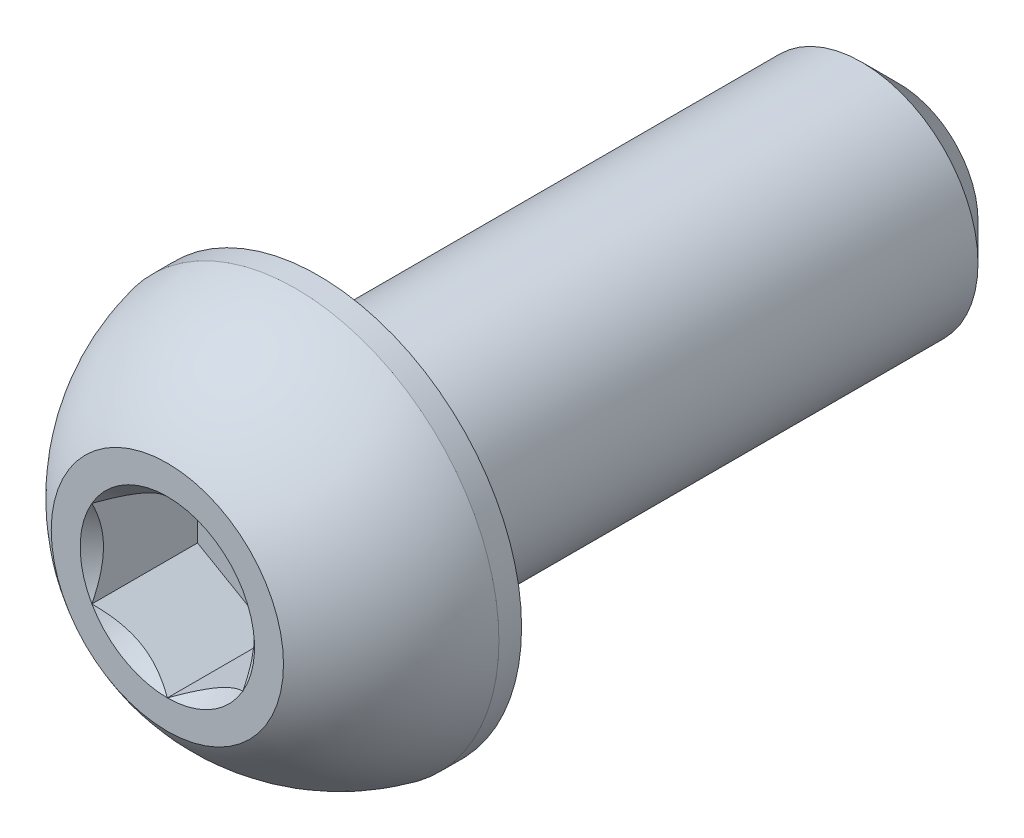
SolidWorks part; units mm, degrees
material "Alloy Steel"
ref_plane "Front Plane" through (0, 0, 0) normal (0, 0, 1) x (1, 0, 0)
ref_plane "Top Plane" through (0, 0, 0) normal (0, 1, 0) x (1, 0, 0)
ref_plane "Right Plane" through (0, 0, 0) normal (1, 0, 0) x (0, 0, -1)
sketch "Sketch1" plane through (0, 0, 0) normal (1, 0, 0) x (0, 0, -1)
  line L0 (-3.15, 0) -> (3.15, 0) construction
  line L1 (-1.85, 1.75) -> (-1.85, -1.75) construction
  line L2 (3.15, 1) -> (3.15, -1) construction
  line L3 (3.125, 1.0433) -> (3.325, 0.6969) construction
  line L4 (3.325, 0.6969) -> (3.525, 1.0433) construction
  line L5 (3.525, 1.0433) -> (3.125, 1.0433) construction
  line L6 (3.15, 1) -> (3.5, 1) construction
  line L7 (3.325, 1.0433) -> (3.325, 1) construction
  line L8 (3.325, 1) -> (3.325, 0.7402) construction
  line L9 (3.325, 0.7402) -> (3.325, 0.6969) construction
  line L10 (3.3, 0.7402) -> (3.35, 0.7402)
  line L11 (3.1375, 1.0217) -> (3.5125, 1.0217)
  line L12 (3.35, 0.7402) -> (3.5125, 1.0217)
  line L13 (3.3, 0.7402) -> (3.1375, 1.0217)
  line L14 (-3.15, 0.65) -> (-3.15, -0.65) construction
  line L15 (3.15, 1) -> (-1.85, 1) construction
  point P3 (-1.85, 0)
  point P6 (-2.24, 0)
  point P21 (3.325, 1.0217)
  point P24 (-2.045, 1.75)
  point P25 (2.15, -1)
  point P26 (-3.15, 1)
  dimension "Head Height" = 1.3
  dimension "Length" = 5
  dimension "Head Dia" = 3.5
  dimension "Thread Dia" = 2
  dimension "Pitch" = 0.4
  dimension "D2" = 0.05
  dimension "Drive Size" = 1.3
  dimension "D1" = 0.91
  dimension "D3" = 0.195
  dimension "D4" = 1
sketch "Sketch2" plane through (0, 0, 0) normal (1, 0, 0) x (0, 0, -1)
  line L0 (-3.15, 0) -> (3.15, 0)
  line L1 (3.15, 0) -> (3.15, 0.68)
  line L2 (3.15, 1) -> (3.15, -1) construction
  line L3 (3.15, 0.68) -> (2.83, 1)
  line L4 (2.83, 1) -> (-1.85, 1)
  line L5 (-1.85, 1.75) -> (-1.85, -1.75) construction
  line L6 (-1.85, 1) -> (-1.85, 1.75)
  line L7 (-1.85, 1.75) -> (-2.045, 1.75)
  line L8 (3.15, 1) -> (3.5, 1) construction
  line L9 (-3.15, 0) -> (-3.15, 1)
  arc A0 (-3.15, 1) -> (-2.045, 1.75) centre (-1.6642, 0) cw
  dimension "D1" = 0.32
  dimension "D2" = 45
revolve "Revolve1" add sketch "Sketch2" angle 360 about L0
sketch "Sketch3" plane through (0, 0, 3.15) normal (0, 0, 1) x (1, 0, 0)
  line L1 (0, 0.7506) -> (-0.65, 0.3753)
  line L2 (-0.65, 0.3753) -> (-0.65, -0.3753)
  line L3 (-0.65, -0.3753) -> (0, -0.7506)
  line L4 (0, -0.7506) -> (0.65, -0.3753)
  line L5 (0.65, -0.3753) -> (0.65, 0.3753)
  line L6 (0.65, 0.3753) -> (0, 0.7506)
  circle A0 centre (0, 0) radius 0.65 construction
  dimension "D1" = 1.3
extrude "Cut-Extrude1" cut sketch "Sketch3" against normal up to vertex (0.91 mm away) up to point (0, 0, 2.24)
sketch "Sketch4" plane through (0, 0, 3.15) normal (0, 0, 1) x (1, 0, 0)
  circle A0 centre (0, 0) radius 0.7506
extrude "Cut-Extrude2" cut sketch "Sketch4" against normal blind 10 draft 45
split "Split1" [suppressed] bodies to split 106
sketch "Sketch5" [suppressed] plane through (0, 0, -3.15) normal (0, 0, -1) x (-1, 0, 0)
  circle A0 centre (0, 0) radius 1 construction
  circle A1 centre (0, 0) radius 1
curve "Helix/Spiral1" [suppressed] pitch 0.4 height 5.4 turns 13.5
sketch "Sketch6" [suppressed] plane through (0, 0, 0) normal (1, 0, 0) x (0, 0, -1)
  line L0 (3.3, 0.7402) -> (3.35, 0.7402) construction
  line L1 (3.3, 0.7402) -> (3.1375, 1.0217) construction
  line L2 (3.1375, 1.0217) -> (3.5125, 1.0217) construction
  line L3 (3.35, 0.7402) -> (3.5125, 1.0217) construction
  line L4 (3.3, 0.7402) -> (3.35, 0.7402)
  line L5 (3.3, 0.7402) -> (3.1375, 1.0217)
  line L6 (3.1375, 1.0217) -> (3.5125, 1.0217)
  line L7 (3.35, 0.7402) -> (3.5125, 1.0217)
sweep "Cut-Sweep1" [suppressed] cut profiles "Sketch6" path "Helix/Spiral1"
sketch "Sketch7" [suppressed] plane through (0, 0, 1.85) normal (0, 0, -1) x (-1, 0, 0)
  circle A1 centre (0, 0) radius 1
  circle A2 centre (0, 0) radius 1
  dimension "D1" = 0
extrude "Boss-Extrude1" [suppressed] add sketch "Sketch7" along normal blind 10 draft 30
equation "\"D2@Sketch1\" = \"Pitch@Sketch1\" / 8"
equation "\"D1@Sketch1\"=\"Drive Size@Sketch1\"*.7"
equation "\"D3@Sketch1\"=\"Head Height@Sketch1\"*.15"
equation "\"D1@Sketch2\"=\"Pitch@Sketch1\"*.8"
equation "\"D1@Sketch3\"=\"Drive Size@Sketch1\""
equation "\"D4@Helix/Spiral1\"=\"Pitch@Sketch1\""
equation "\"D3@Helix/Spiral1\"=\"Length@Sketch1\"+\"Pitch@Sketch1\""
equation "\"D4@Sketch1\"=\"Pitch@Sketch1\"*2.5"
